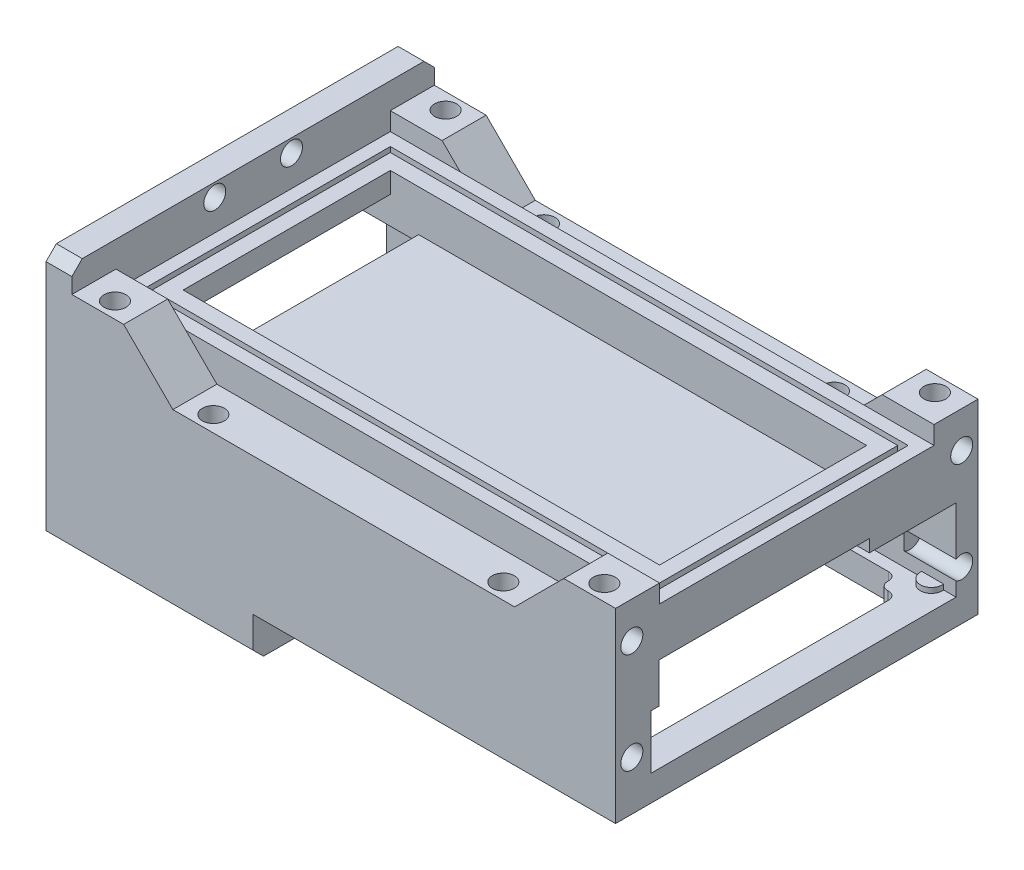
SolidWorks part; units mm, degrees
note: The reader was unsure of these and kept them because the rebuilt part matched: shared geometry of "Sketch26<3>".
ref_plane "Front Plane" through (0, 0, 0) normal (0, 0, 1) x (1, 0, 0)
ref_plane "Top Plane" through (0, 0, 0) normal (0, 1, 0) x (1, 0, 0)
ref_plane "Right Plane" through (0, 0, 0) normal (1, 0, 0) x (0, 0, -1)
sketch "Sketch1" plane through (0, 0, 0) normal (0, 0, 1) x (1, 0, 0)
  line L0 (-105, 9.5) -> (-95, 9.5)
  line L1 (-95, 9.5) -> (-85.5, 0)
  line L2 (-85.5, 0) -> (-19.5, 0)
  line L3 (-19.5, 0) -> (-10, 9.5)
  line L4 (-10, 9.5) -> (0, 9.5)
  line L5 (0, 9.5) -> (0, -30.5)
  line L6 (0, -30.5) -> (-105, -30.5)
  line L7 (-105, -30.5) -> (-105, 9.5)
  dimension "D1" = 40
extrude "Boss-Extrude1" add sketch "Sketch1" against normal blind 70
sketch "Sketch2" plane through (0, 0, 0) normal (1, 0, 0) x (0, 0, -1)
  line L0 (70, 9.5) -> (0, 9.5) construction
  line L1 (8.5, 6) -> (61.5, 6)
  line L2 (8.5, 6) -> (8.5, 9.5)
  line L3 (8.5, 9.5) -> (61.5, 9.5)
  line L4 (61.5, 6) -> (61.5, 9.5)
  line L5 (61.5, 9.5) -> (61.5, 6) construction
extrude "Cut-Extrude1" cut sketch "Sketch2" against normal through all
sketch "Sketch3" plane through (0, 6, 0) normal (0, 1, 0) x (1, 0, 0)
  line L1 (-13.5, 61.5) -> (-91.5, 61.5)
  line L2 (-13.5, 61.5) -> (-13.5, 8.5)
  line L3 (-13.5, 8.5) -> (-91.5, 8.5)
  line L4 (-91.5, 61.5) -> (-91.5, 8.5)
extrude "Boss-Extrude2" add sketch "Sketch3" against normal up to next
sketch "Sketch4" plane through (0, 6, 0) normal (0, 1, 0) x (1, 0, 0)
  line L0 (-10, 61.5) -> (-13.5, 61.5) construction
  line L1 (-6.5, 55) -> (-98.5, 55)
  line L2 (-6.5, 55) -> (-6.5, 15)
  line L3 (-6.5, 15) -> (-98.5, 15)
  line L4 (-98.5, 55) -> (-98.5, 15)
  line L5 (0, 8.5) -> (0, 61.5) construction
  line L6 (-10, 8.5) -> (0, 8.5) construction
  line L7 (-105, 8.5) -> (-105, 61.5) construction
  dimension "D1" = 6.5
  dimension "D2" = 6.5
  dimension "D3" = 6.5
  dimension "D4" = 6.5
extrude "Cut-Extrude2" cut sketch "Sketch4" against normal blind 8 contours L3 L4 L1 L2
sketch "Sketch5" plane through (0, 6, 0) normal (0, 1, 0) x (1, 0, 0)
  line L16 (-102.5, 11) -> (-91.5, 11)
  line L17 (-91.5, 11) -> (-13.5, 11)
  line L18 (-13.5, 11) -> (-2.5, 11)
  line L19 (-2.5, 11) -> (-2.5, 59)
  line L20 (-2.5, 59) -> (-13.5, 59)
  line L21 (-13.5, 59) -> (-91.5, 59)
  line L22 (-91.5, 59) -> (-102.5, 59)
  line L23 (-102.5, 59) -> (-102.5, 11)
  line L24 (-102.5, 11) -> (-91.5, 11)
  line L25 (-91.5, 11) -> (-13.5, 11)
  line L26 (-13.5, 11) -> (-2.5, 11)
  line L27 (-2.5, 11) -> (-2.5, 59)
  line L28 (-2.5, 59) -> (-13.5, 59)
  line L29 (-13.5, 59) -> (-91.5, 59)
  line L30 (-91.5, 59) -> (-102.5, 59)
  line L31 (-102.5, 59) -> (-102.5, 11)
  line L40 (-101.5, 12) -> (-91.5, 12)
  line L41 (-91.5, 12) -> (-13.5, 12)
  line L42 (-13.5, 12) -> (-3.5, 12)
  line L43 (-3.5, 12) -> (-3.5, 58)
  line L44 (-3.5, 58) -> (-13.5, 58)
  line L45 (-13.5, 58) -> (-91.5, 58)
  line L46 (-91.5, 58) -> (-101.5, 58)
  line L47 (-101.5, 58) -> (-101.5, 12)
  line L48 (-101.5, 12) -> (-91.5, 12)
  line L49 (-91.5, 12) -> (-13.5, 12)
  line L50 (-13.5, 12) -> (-3.5, 12)
  line L51 (-3.5, 12) -> (-3.5, 58)
  line L52 (-3.5, 58) -> (-13.5, 58)
  line L53 (-13.5, 58) -> (-91.5, 58)
  line L54 (-91.5, 58) -> (-101.5, 58)
  line L55 (-101.5, 58) -> (-101.5, 12)
  dimension "D1" = 2.5
  dimension "D2" = 3.5
extrude "Cut-Extrude3" cut sketch "Sketch5" against normal blind 2
sketch "Sketch6" plane through (0, -30.5, 0) normal (0, -1, 0) x (-1, 0, 0)
  line L1 (57.7635, 63.9854) -> (12.8388, 63.9854)
  line L2 (57.7635, 63.9854) -> (57.7635, 6.0587)
  line L3 (57.7635, 6.0587) -> (12.8388, 6.0587)
  line L4 (12.8388, 63.9854) -> (12.8388, 6.0587)
  line L6 (0, 70) -> (70, 70)
  line L7 (0, 70) -> (0, 0)
  line L8 (0, 0) -> (70, 0)
  line L9 (70, 70) -> (70, 0)
  line L11 (105, 0) -> (0, 0) construction
  line L12 (0, 70) -> (0, 0) construction
  line M5 (0, 0) -> (105, 0)
  line M7 (105, 70) -> (0, 70)
  dimension "D1" = 70
  dimension "D2" = 70
  dimension "D3" = 0
extrude "Cut-Extrude4" cut sketch "Sketch6" against normal blind 9 contours L1 L4 L3 L2 | L9 L7 L4 L1 L2 L3 M7 M5
sketch "Sketch7" plane through (0, 0, 0) normal (1, 0, 0) x (0, 0, -1)
  line L1 (6.8432, -21.5) -> (65.7561, -21.5)
  line L2 (6.8432, -21.5) -> (6.8432, -11.0466)
  line L3 (6.8432, -11.0466) -> (65.7561, -11.0466)
  line L4 (65.7561, -21.5) -> (65.7561, -11.0466)
  line L5 (35, -30.5) -> (35, 14.8304) construction
  line L6 (70, -30.5) -> (0, -30.5) construction
  line L7 (70, -21.5) -> (0, -21.5) construction
  line L8 (8.3994, -11.0466) -> (8.3994, -3.3244)
  line L9 (8.3994, -3.3244) -> (49.0173, -3.3244)
  line L10 (49.0173, -3.3244) -> (49.0173, -11.0466)
  line L11 (49.0173, -11.0466) -> (47.8262, -11.0466)
  line L12 (47.8262, -11.0466) -> (47.8262, -5.7283)
  line L13 (47.8262, -5.7283) -> (65.7561, -5.7283)
  line L14 (65.7561, -5.7283) -> (65.7561, -11.0466)
  line M14 (0, -21.5) -> (70, -21.5)
extrude "Cut-Extrude5" cut sketch "Sketch7" against normal blind 51 contours L14 L13 L12 L3 | L5 L1 L4 L3 L11 | L5 L3 L2 M14 | L3 L5 L9 L8 | L5 L3 L12 L13 L10 L9 | L13 L12 L3 L10
sketch "Sketch9" plane through (0, -21.5, 0) normal (0, -1, 0) x (1, 0, 0)
  line L0 (-51, -6.8432) -> (-73.8733, -6.8432)
  line L1 (-73.8733, -6.8432) -> (-105, -6.8432)
  line L2 (-105, -70) -> (-105, 0) construction
  line L7 (-51, -65.75) -> (-51, -6.8432)
  line L8 (-51, -6.8432) -> (-51, -65.7561) construction
  line L10 (-51, -65.75) -> (-105, -65.75)
  line L11 (-105, -70) -> (-105, -61.5) construction
  line L12 (-105, -65.75) -> (-105, -6.8432)
extrude "Cut-Extrude6" cut sketch "Sketch9" against normal up to surface (18.1756 mm away) contours L7 L0 L1 L12 L10 up to face at (-25.5, -3.3244, -28.7084)
sketch "Sketch11" plane through (0, 0, -15) normal (0, 0, -1) x (-1, 0, 0)
  line L0 (98.5, 2) -> (105, -2.6376)
  line L1 (98.5, -2) -> (98.5, 6) construction
  line L2 (105, 9.5) -> (105, -30.5) construction
  line L3 (105, -2.6376) -> (105, -11.163)
  line L4 (105, -11.163) -> (93.0281, -11.163)
  line L6 (93.0281, -11.163) -> (93.0281, -2)
  line L7 (6.5, -2) -> (98.5, -2) construction
  line L8 (93.0281, -2) -> (98.5, -2)
  line L9 (98.5, -2) -> (98.5, 2)
  line M9 (6.5, -2) -> (98.5, -2)
  line M10 (98.5, -2) -> (98.5, 6)
extrude "Cut-Extrude8" cut sketch "Sketch11" along normal up to surface (40 mm away) contours L6 L4 L3 L0 M10 M9 up to face at (-52.5, 2, -55)
sketch "Sketch12" plane through (0, -21.5, 0) normal (0, -1, 0) x (1, 0, 0)
  line L1 (-63, -60.25) -> (-6, -60.25)
  line L2 (-63, -60.25) -> (-63, -9.75)
  line L3 (-63, -9.75) -> (-6, -9.75)
  line L4 (-6, -60.25) -> (-6, -9.75)
  line L5 (-59.75, -63.5) -> (-9.25, -63.5)
  line L6 (-59.75, -63.5) -> (-59.75, -6.5)
  line L7 (-59.75, -6.5) -> (-9.25, -6.5)
  line L8 (-9.25, -63.5) -> (-9.25, -6.5)
  line L10 (0, -8.3994) -> (0, -6.8432) construction
  line L11 (0, -70) -> (0, 0)
  line L16 (0, 0) -> (-70, 0)
  line L17 (-70, 0) -> (-70, -70)
  line L18 (-70, -70) -> (0, -70)
  point P10 (-34.5, -9.75)
  point P11 (-34.5, -6.5)
  point P21 (-9.25, -35)
  point P22 (-6, -35)
  point P23 (-70, -35)
  point P28 (-63, -35)
  line M13 (-70, 0) -> (-70, -6.8432)
  line M14 (-70, -6.8432) -> (0, -6.8432)
  line M15 (0, -6.8432) -> (0, 0)
  line M16 (0, 0) -> (-70, 0)
  dimension "D1" = 50.5
  dimension "D2" = 57
  dimension "D3" = 50.5
  dimension "D4" = 57
  dimension "D5" = 6
extrude "Boss-Extrude11" add sketch "Sketch12" along normal blind 5 contours L17 L18 L11 L8 L5 L6 L1 L2 L3 L7 L4 M14 | M16 M13 M14 M15
sketch "Sketch13" plane through (0, -26.5, 0) normal (0, -1, 0) x (1, 0, 0)
  line L0 (0, -70) -> (0, 0) construction
  line L1 (-65.5, -4.5) -> (-4.5, -4.5) construction
  line L2 (-65.5, -4.5) -> (-65.5, -65.5) construction
  line L3 (-65.5, -65.5) -> (-4.5, -65.5) construction
  line L4 (-4.5, -4.5) -> (-4.5, -65.5) construction
  line L5 (0, 0) -> (-70, 0) construction
  circle A0 centre (-65.5, -4.5) radius 2.125
  circle A1 centre (-65.5, -65.5) radius 2.125
  circle A2 centre (-4.5, -65.5) radius 2.125
  circle A3 centre (-4.5, -4.5) radius 2.125
  point P6 (0, -35)
  point P7 (-4.5, -35)
  point P10 (-35, 0)
  point P11 (-35, -4.5)
  dimension "D3" = 4.25
  dimension "D1" = 61
  dimension "D2" = 61
extrude "Cut-Extrude9" cut sketch "Sketch13" against normal blind 5
fillet "Fillet1" radius 1.5 12 edges at (-9.25, -24, -6.5) (-9.25, -24, -9.75) (-6, -24, -9.75) (-59.75, -24, -6.5) (-59.75, -24, -9.75) (-63, -24, -9.75) (-63, -24, -60.25) (-59.75, -24, -63.5) (-59.75, -24, -60.25) (-6, -24, -60.25) (-9.25, -24, -63.5) (-9.25, -24, -60.25)
sketch "Sketch17" plane through (-105, 0, 0) normal (-1, 0, 0) x (0, 0, 1)
  line L1 (-65.75, -9.4775) -> (-37.75, -9.4775)
  line L2 (-65.75, -9.4775) -> (-65.75, -25.4775)
  line L3 (-65.75, -25.4775) -> (-37.75, -25.4775)
  line L4 (-37.75, -9.4775) -> (-37.75, -25.4775)
  dimension "D1" = 16
  dimension "D2" = 28
extrude "Cut-Extrude13" cut sketch "Sketch17" against normal blind 33
sketch "Sketch18" plane through (0, -26.5, 0) normal (0, -1, 0) x (1, 0, 0)
  line L0 (-64.5, -11.25) -> (-64.5, -58.75)
  line L1 (-61.5, -61.75) -> (-61.25, -61.75)
  line L2 (-61.25, -61.75) -> (-61.25, -62)
  line L3 (-58.25, -65) -> (-10.75, -65)
  line L4 (-7.75, -62) -> (-7.75, -61.75)
  line L5 (-7.75, -61.75) -> (-7.5, -61.75)
  line L6 (-4.5, -58.75) -> (-4.5, -11.25)
  line L7 (-7.5, -8.25) -> (-7.75, -8.25)
  line L8 (-7.75, -8.25) -> (-7.75, -8)
  line L9 (-10.75, -5) -> (-58.25, -5)
  line L10 (-61.25, -8) -> (-61.25, -8.25)
  line L11 (-61.25, -8.25) -> (-61.5, -8.25)
  line L12 (-9.25, -8.25) -> (-9.25, -8)
  line L13 (-7.5, -9.75) -> (-7.75, -9.75)
  line L14 (-9.25, -8.25) -> (-9.25, -8)
  line L15 (-7.75, -60.25) -> (-7.5, -60.25)
  line L16 (-6, -58.75) -> (-6, -11.25)
  line L17 (-58.25, -63.5) -> (-10.75, -63.5)
  line L18 (-59.75, -61.75) -> (-59.75, -62)
  line L19 (-6, -58.75) -> (-6, -11.25)
  line L20 (-63, -11.25) -> (-63, -58.75)
  line L21 (-9.25, -62) -> (-9.25, -61.75)
  line L22 (-59.75, -8) -> (-59.75, -8.25)
  line L23 (-10.75, -6.5) -> (-58.25, -6.5)
  line L25 (-7.5, -9.75) -> (-7.75, -9.75)
  line L27 (-7.75, -60.25) -> (-7.5, -60.25)
  line L29 (-58.25, -63.5) -> (-10.75, -63.5)
  line L30 (-59.75, -61.75) -> (-59.75, -62)
  line L32 (-63, -11.25) -> (-63, -58.75)
  line L34 (-59.75, -8) -> (-59.75, -8.25)
  line L35 (-10.75, -6.5) -> (-58.25, -6.5)
  line L36 (-65.5, -11.25) -> (-65.5, -58.75)
  line L37 (-62.19, -62.69) -> (-62.19, -62.69)
  line L38 (-62.19, -62.69) -> (-62.19, -62.69)
  line L39 (-58.25, -66) -> (-10.75, -66)
  line L40 (-6.81, -62.69) -> (-6.81, -62.69)
  line L41 (-6.81, -62.69) -> (-6.81, -62.69)
  line L42 (-3.5, -58.75) -> (-3.5, -11.25)
  line L43 (-6.81, -7.31) -> (-6.81, -7.31)
  line L44 (-6.81, -7.31) -> (-6.81, -7.31)
  line L45 (-10.75, -4) -> (-58.25, -4)
  line L46 (-62.19, -7.31) -> (-62.19, -7.31)
  line L47 (-62.19, -7.31) -> (-62.19, -7.31)
  line L60 (-9.25, -62) -> (-9.25, -61.75)
  line L61 (-61.5, -60.25) -> (-61.25, -60.25)
  line L62 (-9.25, -8.25) -> (-9.25, -8) construction
  line L63 (-6, -58.75) -> (-6, -11.25) construction
  line L64 (-9.25, -62) -> (-9.25, -61.75) construction
  line L65 (-61.5, -60.25) -> (-61.25, -60.25) construction
  line L66 (-61.25, -9.75) -> (-61.5, -9.75) construction
  line L67 (-61.5, -60.25) -> (-61.25, -60.25)
  line L68 (-61.25, -9.75) -> (-61.5, -9.75)
  line L69 (-61.25, -9.75) -> (-61.5, -9.75)
  arc A0 (-64.5, -58.75) -> (-61.5, -61.75) centre (-61.5, -58.75) ccw
  arc A1 (-61.25, -61.75) -> (-61.25, -61.75) centre (-61.25, -61.75) ccw
  arc A3 (-61.25, -62) -> (-58.25, -65) centre (-58.25, -62) ccw
  arc A5 (-10.75, -65) -> (-7.75, -62) centre (-10.75, -62) ccw
  arc A7 (-7.75, -61.75) -> (-7.75, -61.75) centre (-7.75, -61.75) ccw
  arc A9 (-7.5, -61.75) -> (-4.5, -58.75) centre (-7.5, -58.75) ccw
  arc A10 (-4.5, -11.25) -> (-7.5, -8.25) centre (-7.5, -11.25) ccw
  arc A11 (-7.75, -8.25) -> (-7.75, -8.25) centre (-7.75, -8.25) ccw
  arc A17 (-59.75, -62) -> (-58.25, -63.5) centre (-58.25, -62) ccw
  arc A18 (-59.75, -61.75) -> (-61.25, -60.25) centre (-61.25, -61.75) ccw
  arc A19 (-63, -58.75) -> (-61.5, -60.25) centre (-61.5, -58.75) ccw
  arc A20 (-61.5, -9.75) -> (-63, -11.25) centre (-61.5, -11.25) ccw
  arc A21 (-61.25, -9.75) -> (-59.75, -8.25) centre (-61.25, -8.25) ccw
  arc A22 (-58.25, -6.5) -> (-59.75, -8) centre (-58.25, -8) ccw
  arc A29 (-59.75, -62) -> (-58.25, -63.5) centre (-58.25, -62) ccw
  arc A30 (-59.75, -61.75) -> (-61.25, -60.25) centre (-61.25, -61.75) ccw
  arc A31 (-63, -58.75) -> (-61.5, -60.25) centre (-61.5, -58.75) ccw
  arc A32 (-61.5, -9.75) -> (-63, -11.25) centre (-61.5, -11.25) ccw
  arc A33 (-61.25, -9.75) -> (-59.75, -8.25) centre (-61.25, -8.25) ccw
  arc A34 (-58.25, -6.5) -> (-59.75, -8) centre (-58.25, -8) ccw
  arc A36 (-7.75, -8) -> (-10.75, -5) centre (-10.75, -8) ccw
  arc A37 (-58.25, -5) -> (-61.25, -8) centre (-58.25, -8) ccw
  arc A38 (-61.25, -8.25) -> (-61.25, -8.25) centre (-61.25, -8.25) ccw
  arc A39 (-61.5, -8.25) -> (-64.5, -11.25) centre (-61.5, -11.25) ccw
  arc A40 (-65.5, -58.75) -> (-62.19, -62.69) centre (-61.5, -58.75) ccw
  arc A41 (-62.19, -62.69) -> (-62.19, -62.69) centre (-62.19, -62.69) ccw
  arc A42 (-62.19, -62.69) -> (-58.25, -66) centre (-58.25, -62) ccw
  arc A43 (-10.75, -66) -> (-6.81, -62.69) centre (-10.75, -62) ccw
  arc A44 (-6.81, -62.69) -> (-6.81, -62.69) centre (-6.81, -62.69) ccw
  arc A45 (-6.81, -62.69) -> (-3.5, -58.75) centre (-7.5, -58.75) ccw
  arc A46 (-3.5, -11.25) -> (-6.81, -7.31) centre (-7.5, -11.25) ccw
  arc A47 (-6.81, -7.31) -> (-6.81, -7.31) centre (-6.81, -7.31) ccw
  arc A48 (-6.81, -7.31) -> (-10.75, -4) centre (-10.75, -8) ccw
  arc A49 (-58.25, -4) -> (-62.19, -7.31) centre (-58.25, -8) ccw
  arc A50 (-62.19, -7.31) -> (-62.19, -7.31) centre (-62.19, -7.31) ccw
  arc A51 (-62.19, -7.31) -> (-65.5, -11.25) centre (-61.5, -11.25) ccw
  arc A58 (-9.25, -8.25) -> (-7.75, -9.75) centre (-7.75, -8.25) ccw
  arc A59 (-9.25, -8.25) -> (-7.75, -9.75) centre (-7.75, -8.25) ccw
  arc A60 (-6, -11.25) -> (-7.5, -9.75) centre (-7.5, -11.25) ccw
  arc A61 (-6, -11.25) -> (-7.5, -9.75) centre (-7.5, -11.25) ccw
  arc A62 (-7.5, -60.25) -> (-6, -58.75) centre (-7.5, -58.75) ccw
  arc A63 (-7.5, -60.25) -> (-6, -58.75) centre (-7.5, -58.75) ccw
  arc A64 (-9.25, -8.25) -> (-7.75, -9.75) centre (-7.75, -8.25) ccw construction
  arc A65 (-6, -11.25) -> (-7.5, -9.75) centre (-7.5, -11.25) ccw construction
  arc A66 (-7.5, -60.25) -> (-6, -58.75) centre (-7.5, -58.75) ccw construction
  arc A67 (-7.75, -60.25) -> (-9.25, -61.75) centre (-7.75, -61.75) ccw construction
  arc A68 (-10.75, -63.5) -> (-9.25, -62) centre (-10.75, -62) ccw construction
  arc A69 (-9.25, -8) -> (-10.75, -6.5) centre (-10.75, -8) ccw construction
  arc A70 (-7.75, -60.25) -> (-9.25, -61.75) centre (-7.75, -61.75) ccw
  arc A71 (-7.75, -60.25) -> (-9.25, -61.75) centre (-7.75, -61.75) ccw
  arc A72 (-10.75, -63.5) -> (-9.25, -62) centre (-10.75, -62) ccw
  arc A73 (-10.75, -63.5) -> (-9.25, -62) centre (-10.75, -62) ccw
  arc A74 (-9.25, -8) -> (-10.75, -6.5) centre (-10.75, -8) ccw
  arc A75 (-9.25, -8) -> (-10.75, -6.5) centre (-10.75, -8) ccw
  dimension "D1" = 0
  dimension "D2" = 1.5
  dimension "D3" = 2.5
extrude "Cut-Extrude14" cut sketch "Sketch18" against normal blind 2 contours A49 A51 L36 A40 A42 L39 A43 A45 L42 A46 A48 L45 A39 L11 L10 A37 L9 A36 L8 L7 A10 L6 A9 L5 L4 A5 L3 A3 L2 L1 A0 L0
fillet "Fillet2" radius 7.5 8 edges at (-6.81, -25.5, -7.31) (-62.19, -25.5, -7.31) (-61.25, -25.5, -61.75) (-7.75, -25.5, -61.75) (-7.75, -25.5, -8.25) (-61.25, -25.5, -8.25) (-6.81, -25.5, -62.69) (-62.19, -25.5, -62.69)
sketch "Sketch19" plane through (-105, 0, 0) normal (1, 0, 0) x (0, 0, -1)
  line L12 (0, -26.5) -> (0, 9.5) construction
  line L13 (0, 14.5) -> (70, 14.5)
  line L14 (0, 14.5) -> (0, -30.5)
  line L15 (0, -30.5) -> (70, -30.5)
  line L16 (70, 14.5) -> (70, -30.5)
  line L17 (70, -26.5) -> (70, 9.5) construction
  line L18 (8.5, 9.5) -> (0, 9.5) construction
  dimension "D1" = 45
  dimension "D2" = 5
extrude "Boss-Extrude12" add sketch "Sketch19" against normal blind 5
sketch "Sketch20" plane through (0, -30.5, 0) normal (0, -1, 0) x (1, 0, 0)
  line L4 (-110, -70) -> (-70, -70)
  line L5 (-70, -70) -> (-70, 0)
  line L6 (-70, 0) -> (-110, 0)
  line L7 (-110, 0) -> (-110, -70)
  line L8 (-110, -70) -> (-70, -70)
  line L9 (-70, -70) -> (-70, 0)
  line L10 (-70, 0) -> (-110, 0)
  line L11 (-110, 0) -> (-110, -70)
  dimension "D1" = 0
extrude "Boss-Extrude13" add sketch "Sketch20" along normal blind 4
chamfer "Chamfer1" distance 2 angle 45 4 edges at (-107.5, 14.5, -70) (-107.5, 14.5, 0) (-90, -34.5, 0) (-90, -34.5, -70)
sketch "Sketch21" plane through (-110, 0, 0) normal (-1, 0, 0) x (0, 0, 1)
  circle A0 centre (-67.5111, -10.1907) radius 2.125
  circle A1 centre (-67.5111, -31.9774) radius 2.125
  circle A2 centre (-43.0884, -31.8539) radius 2.125
  circle A3 centre (-26.9116, -31.8539) radius 2.125
  circle A4 centre (-2.4889, -31.9774) radius 2.125
  circle A5 centre (-2.4889, -10.1907) radius 2.125
  circle A6 centre (-27.5887, 11.9433) radius 2.125
  circle A7 centre (-42.4113, 11.9433) radius 2.125
  dimension "D1" = 4.25
extrude "Cut-Extrude15" cut sketch "Sketch21" against normal blind 5
sketch "Sketch22" plane through (0, -3.3244, 0) normal (0, -1, 0) x (1, 0, 0)
  line L1 (-64.9511, -50.196) -> (-57.1691, -50.196)
  line L2 (-64.9511, -50.196) -> (-64.9511, -23.636)
  line L3 (-64.9511, -23.636) -> (-57.1691, -23.636)
  line L4 (-57.1691, -50.196) -> (-57.1691, -23.636)
extrude "Boss-Extrude14" add sketch "Sketch22" along normal blind 14.5
sketch "Sketch23" plane through (0, -17.8244, 0) normal (0, -1, 0) x (1, 0, 0)
  line L1 (-60.0397, -28.1165) -> (-57.1691, -28.1165)
  line L2 (-60.0397, -28.1165) -> (-60.0397, -23.636)
  line L3 (-60.0397, -23.636) -> (-57.1691, -23.636)
  line L4 (-57.1691, -28.1165) -> (-57.1691, -23.636)
  circle A0 centre (-61.3196, -47.4848) radius 1
  circle A1 centre (-61.3196, -26.4848) radius 1
extrude "Cut-Extrude16" cut sketch "Sketch23" against normal blind 5
chamfer "Chamfer2" distance 10 distance2 14.4 1 edges at (-57.1691, -3.3244, -36.916)
chamfer "Chamfer3" distance 6 angle 45 1 edges at (-50.4678, -8.0744, -23.636)
sketch "Sketch24" plane through (0, 0, 0) normal (1, 0, 0) x (0, 0, -1)
  circle A0 centre (3.1444, -16.9723) radius 2.125
  circle A1 centre (3.1444, 2.4841) radius 2.125
  circle A2 centre (66.8556, 2.4841) radius 2.125
  circle A3 centre (66.8556, -16.9723) radius 2.125
  dimension "D1" = 4.25
extrude "Cut-Extrude17" cut sketch "Sketch24" against normal blind 10
sketch "Sketch25" plane through (0, -21.5, 0) normal (0, -1, 0) x (1, 0, 0)
  circle A0 centre (-4.5, -65.5) radius 2.125
  circle A1 centre (-65.5, -65.5) radius 2.125
extrude "Boss-Extrude15" add sketch "Sketch25" against normal blind 1 and the other way blind 0.1 contours A1 | A0
sketch "Sketch26" plane through (0, 9.5, 0) normal (0, 1, 0) x (1, 0, 0)
  circle A0 centre (-5.25, 66.925) radius 2.125
  circle A1 centre (-5.25, 3.075) radius 2.125
  circle A2 centre (-99.75, 3.075) radius 2.125
  circle A3 centre (-99.75, 66.925) radius 2.125
  circle A4 centre (-80.7574, 66.925) radius 2.125
  circle A5 centre (-24.7574, 66.925) radius 2.125
  circle A6 centre (-24.7574, 3.075) radius 2.125
  circle A7 centre (-80.7574, 3.075) radius 2.125
  dimension "D1" = 4.25
extrude "Cut-Extrude18" cut sketch "Sketch26" against normal blind 5 from surface at -9.5 contours A5 | A4 | A7 | A6 starting at face at (-52.5, 0, -65.75)
extrude "Cut-Extrude19" cut sketch "Sketch26<3>" against normal blind 5 contours A2 | A3 | A0 | A1
sketch "Sketch26<3>" plane through (0, 9.5, 0) normal (0, 1, 0) x (1, 0, 0) same geometry as "Sketch26"
equation "\"D2@Sketch4\"=\"D1@Sketch4\""
equation "\"D3@Sketch4\"=\"D1@Sketch4\""
equation "\"D4@Sketch4\"=\"D1@Sketch4\""
